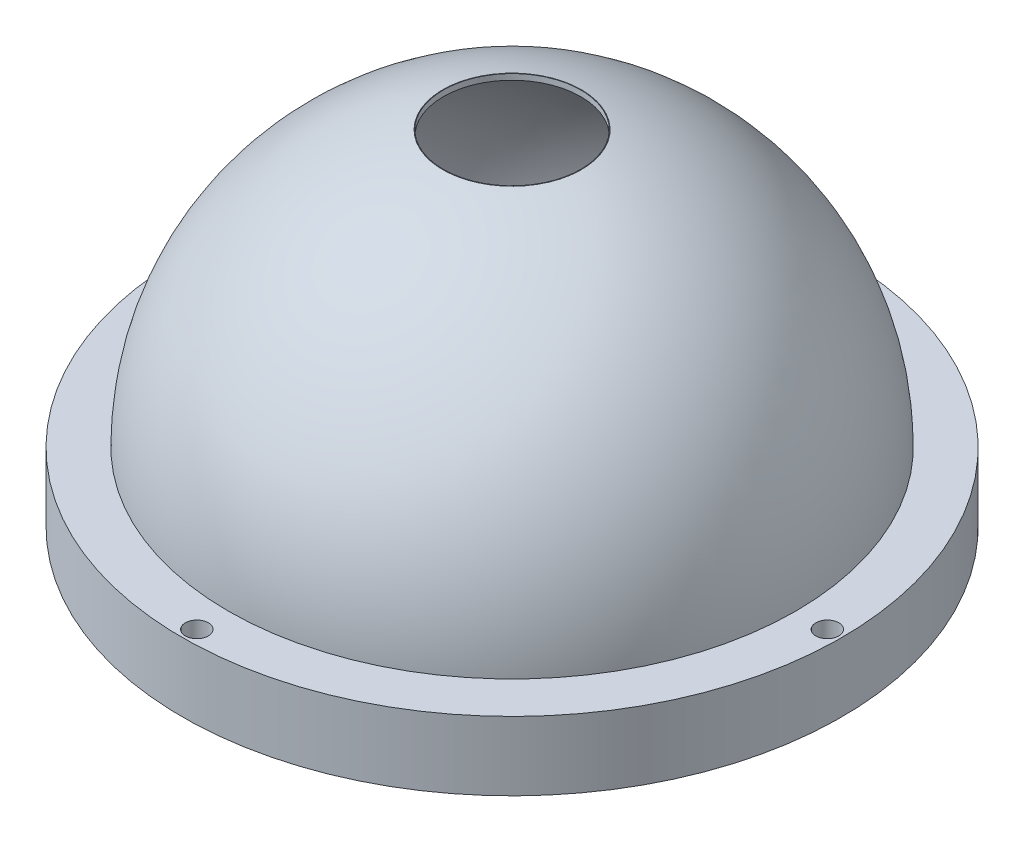
SolidWorks part; units mm, degrees
ref_plane "Front Plane" through (0, 0, 0) normal (0, 0, 1) x (1, 0, 0)
ref_plane "Top Plane" through (0, 0, 0) normal (0, 1, 0) x (1, 0, 0)
ref_plane "Right Plane" through (0, 0, 0) normal (1, 0, 0) x (0, 0, -1)
sketch "Sketch1" plane through (0, 0, 0) normal (0, 0, 1) x (1, 0, 0)
  line L0 (0, -100.5382) -> (0, 66.1215) construction
  line L1 (0, 0) -> (48.5, 0) construction
  line L3 (0, 47) -> (11.9687, 47)
  arc A0 (48.5, 0) -> (11.9687, 47) centre (0, 0) ccw
  point P7 (0, -17.2083)
  dimension "D1" = 47
  dimension "D2" = 48.5
revolve "Revolve-Thin1" add sketch "Sketch1" angle 360 about L0 wall 1
sketch "Sketch2" plane through (0, 48, 0) normal (0, 1, 0) x (1, 0, 0)
  circle A0 centre (0, 0) radius 12
  dimension "D1" = 24
extrude "Cut-Extrude1" cut sketch "Sketch2" against normal up to next
sketch "Sketch3" plane through (0, 0, 0) normal (0, -1, 0) x (1, 0, 0)
  circle A0 centre (0, 0) radius 48.5
  circle A1 centre (0, 0) radius 57.5
  dimension "D1" = 115
  dimension "D2" = 97
extrude "Boss-Extrude1" add sketch "Sketch3" along normal blind 12
sketch "Sketch4" plane through (0, -12, 0) normal (0, -1, 0) x (1, 0, 0)
  line L0 (0, 55) -> (0, -55) construction
  line L1 (55, 0) -> (-55, 0) construction
  circle A0 centre (0, 0) radius 55 construction
  circle A1 centre (0, 55) radius 2
  circle A5 centre (55, 0) radius 2
  circle A6 centre (-55, 0) radius 2
  circle A7 centre (0, -55) radius 2
  point P14 (0, 0)
  dimension "D1" = 110
  dimension "D2" = 4
extrude "Cut-Extrude2" cut sketch "Sketch4" against normal up to next
